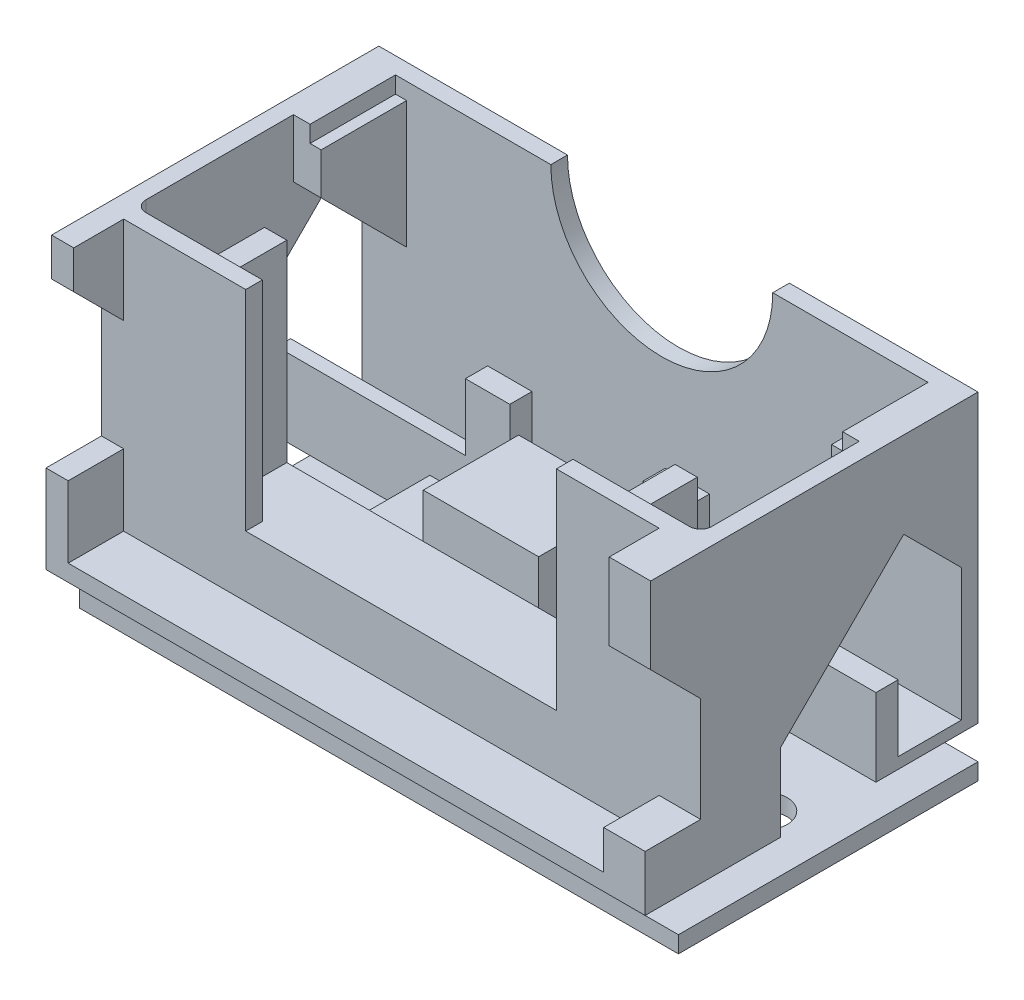
SolidWorks part; units mm, degrees
note: The reader was unsure of these and kept them because the rebuilt part matched: shared geometry of "Sketch4<4>", "Sketch5<3>", "Sketch4<3>", "Sketch17<3>", "Sketch5<4>", "Sketch21<3>".
ref_plane "Front Plane" through (0, 0, 0) normal (0, 0, 1) x (1, 0, 0)
ref_plane "Top Plane" through (0, 0, 0) normal (0, 1, 0) x (1, 0, 0)
ref_plane "Right Plane" through (0, 0, 0) normal (1, 0, 0) x (0, 0, -1)
sketch "Sketch1" plane through (0, 0, 0) normal (0, 1, 0) x (1, 0, 0)
  line L1 (0, 0) -> (54, 0)
  line L2 (0, 0) -> (0, 27)
  line L3 (0, 27) -> (54, 27)
  line L4 (54, 0) -> (54, 27)
  dimension "D1" = 54
  dimension "D2" = 27
extrude "Boss-Extrude1" add sketch "Sketch1" along normal blind 1.5
sketch "Sketch2" plane through (0, 1.5, 0) normal (0, 1, 0) x (1, 0, 0)
  line L0 (0, 27) -> (0, 0) construction
  circle A0 centre (5.8, 13.5) radius 2.1
  point P5 (0, 13.5)
  dimension "D3" = 4.2
  dimension "D1" = 5.8
extrude "Cut-Extrude1" cut sketch "Sketch2" against normal up to next and the other way through all
ref_plane "Plane1" through (27, 0, 0) normal (-1, 0, 0) x (0, 0, 1)
mirror "Mirror1" about plane through (27, 0, 0) normal (-1, 0, 0) of "Cut-Extrude1"
sketch "Sketch3" plane through (0, 1.5, 0) normal (0, 1, 0) x (1, 0, 0)
  line L0 (54, 27) -> (0, 27) construction
  line L1 (13.8, 27) -> (40.2, 27)
  line L2 (13.8, 27) -> (13.8, -3)
  line L3 (13.8, -3) -> (40.2, -3)
  line L4 (40.2, 27) -> (40.2, -3)
  line L7 (0, 0) -> (54, 0) construction
  circle A0 centre (5.8, 13.5) radius 2.1 construction
  point P8 (27, 0)
  point P9 (27, -3)
  dimension "D1" = 8
  dimension "D2" = 3
extrude "Boss-Extrude2" add sketch "Sketch3" along normal blind 3
chamfer "Chamfer3" distance 3 angle 45 1 edges at (27, 1.5, 3)
sketch "Sketch4" plane through (0, 4.5, 0) normal (0, 1, 0) x (1, 0, 0)
  line L0 (54, 0) -> (54, 27) construction
  line L1 (0, 27) -> (54, 27)
  line L2 (0, 27) -> (0, 2)
  line L3 (0, 2) -> (54, 2)
  line L4 (54, 27) -> (54, 2)
  line L5 (0, 27) -> (0, 0) construction
  line L6 (0, 17.8) -> (54, 17.8)
  line L7 (0, 17.8) -> (0, 9.2)
  line L8 (0, 9.2) -> (54, 9.2)
  line L9 (54, 17.8) -> (54, 9.2)
  line L10 (40.2, 27) -> (13.8, 27) construction
  line L11 (0, 27) -> (0, 0) construction
  line L13 (32.2, 17.8) -> (21.8, 17.8)
  line L14 (32.2, 17.8) -> (32.2, 9.2)
  line L15 (32.2, 9.2) -> (21.8, 9.2)
  line L16 (21.8, 17.8) -> (21.8, 9.2)
  line L17 (40.2, 0) -> (54, 0) construction
  point P0 (0, 13.5)
  point P17 (0, 13.5)
  point P23 (27, 17.8)
  point P24 (27, 17.8)
  line M9 (13.8, 27) -> (13.8, -3)
  line M11 (40.2, -3) -> (40.2, 27)
  dimension "D1" = 8.6
  dimension "D2" = 21.8
  dimension "D3" = 2
extrude "Boss-Extrude3" add sketch "Sketch4" along normal blind 7
extrude "Boss-Extrude15" add sketch "Sketch4<4>" along normal blind 4 from surface at 7 contours L6 L16 L8 L14 starting at face at (27, 11.5, -13.8333)
sketch "Sketch4<4>" plane through (0, 4.5, 0) normal (0, 1, 0) x (1, 0, 0) same geometry as "Sketch4"
sketch "Sketch5" plane through (0, 11.5, 0) normal (0, 1, 0) x (1, 0, 0)
  line L0 (54, 9.2) -> (54, 2) construction
  line L1 (54, 2) -> (0, 2)
  line L2 (54, 2) -> (54, 3.5)
  line L3 (54, 3.5) -> (0, 3.5)
  line L4 (0, 2) -> (0, 3.5)
  line L5 (0, 9.2) -> (0, 2) construction
  line L6 (32.2, 9.2) -> (54, 9.2) construction
  line L7 (27, 0.825) -> (27, -0.825) construction
  line L16 (9.5, 9.2) -> (7.5, 9.2)
  line L17 (44.5, 3.5) -> (46.5, 3.5)
  line L18 (44.5, 3.5) -> (44.5, 9.2)
  line L19 (44.5, 9.2) -> (46.5, 9.2)
  line L20 (46.5, 3.5) -> (46.5, 9.2)
  line L21 (7.5, 3.5) -> (7.5, 9.2)
  line L22 (9.5, 3.5) -> (7.5, 3.5)
  line L23 (9.5, 3.5) -> (9.5, 9.2)
  line L27 (52.225, 2) -> (46.225, 2)
  line L29 (1.775, 2) -> (7.775, 2)
  line L33 (0, 27) -> (0, 17.8) construction
  line L34 (54, 27) -> (0, 27)
  line L35 (54, 27) -> (54, 25.5)
  line L36 (54, 25.5) -> (0, 25.5)
  line L37 (0, 27) -> (0, 25.5)
  line M16 (21.8, 9.2) -> (0, 9.2)
  line M20 (54, 9.2) -> (32.2, 9.2)
  dimension "D1" = 22
  dimension "D2" = 1.5
  dimension "D3" = 19.5
  dimension "D4" = 2
  dimension "D7" = 1.5
extrude "Boss-Extrude5" add sketch "Sketch5" along normal offset from surface (18.86 mm away) 25.86 contours L3 L4 L1 L2 up to face at (27, 4.5, 0.5) offset beyond the face yes
extrude "Boss-Extrude6" add sketch "Sketch5<3>" along normal offset from surface (17.36 mm away) 1.5 contours L3 L20 L18 M20 | L3 L23 L21 M16 up to face at (27, 30.36, -2.75)
sketch "Sketch5<3>" plane through (0, 11.5, 0) normal (0, 1, 0) x (1, 0, 0) same geometry as "Sketch5"
extrude "Boss-Extrude12" add sketch "Sketch4<3>" along normal offset from surface (3.86 mm away) 20.5 contours L16 L6 L8 M9 | L6 L14 L8 M11 up to face at (45.5, 28.86, -6.35)
sketch "Sketch4<3>" plane through (0, 4.5, 0) normal (0, 1, 0) x (1, 0, 0) same geometry as "Sketch4"
sketch "Sketch17" plane through (0, 0, -2) normal (0, 0, 1) x (1, 0, 0)
  line L0 (54, 30.36) -> (54, 4.5) construction
  line L1 (0, 4.5) -> (54, 4.5)
  line L2 (0, 4.5) -> (0, 6)
  line L3 (0, 6) -> (54, 6)
  line L4 (54, 4.5) -> (54, 6)
  line L5 (54, 30.36) -> (0, 30.36) construction
  line L10 (0, 30.36) -> (2, 30.36)
  line L11 (0, 30.36) -> (0, 6)
  line L12 (0, 6) -> (2, 6)
  line L13 (2, 30.36) -> (2, 6)
  line L14 (2, 22.43) -> (0, 22.43)
  line L15 (2, 22.43) -> (2, 12.43)
  line L16 (2, 12.43) -> (0, 12.43)
  line L17 (0, 22.43) -> (0, 12.43)
  line L23 (54, 6) -> (50.26, 6)
  line L24 (54, 30.36) -> (50.26, 30.36)
  line L25 (54, 30.36) -> (54, 18.93)
  line L26 (54, 18.93) -> (50.26, 18.93)
  line L27 (50.26, 30.36) -> (50.26, 18.93)
  line L28 (54, 6) -> (54, 9.5)
  line L29 (54, 9.5) -> (50.26, 9.5)
  line L30 (50.26, 6) -> (50.26, 9.5)
  point P18 (2, 17.43)
  point P20 (52.13, 18.93)
  line M21 (0, 4.5) -> (13.8, 4.5)
  line M22 (13.8, 4.5) -> (40.2, 4.5)
  line M23 (40.2, 4.5) -> (54, 4.5)
  line M24 (54, 4.5) -> (54, 30.36)
  line M25 (54, 30.36) -> (0, 30.36)
  line M26 (0, 30.36) -> (0, 4.5)
  dimension "D1" = 1.5
  dimension "D2" = 48.26
  dimension "D3" = 2
  dimension "D4" = 10
  dimension "D5" = 11.43
  dimension "D6" = 11.43
  dimension "D7" = 5
extrude "Boss-Extrude13" add sketch "Sketch17" along normal up to vertex (4 mm away) contours L13 L16 L3 M26 | L3 M26 M21 M22 M23 M24 | L28 L23 L30 L29
extrude "Boss-Extrude16" add sketch "Sketch17<3>" along normal offset from surface (4.5 mm away) 0.5 contours L14 L13 M25 M26 | L27 L26 M25 M24 up to face at (26.652, 7.386, 3)
sketch "Sketch17<3>" plane through (0, 0, -2) normal (0, 0, 1) x (1, 0, 0) same geometry as "Sketch17"
chamfer "Chamfer7" distance 4.5 angle 45 2 edges at (52.13, 18.93, 2.5) (1, 22.43, 2.5)
extrude "Boss-Extrude8" add sketch "Sketch5<4>" along normal up to surface (18.86 mm away)
sketch "Sketch5<4>" plane through (0, 11.5, 0) normal (0, 1, 0) x (1, 0, 0) same geometry as "Sketch5"
sketch "Sketch10" plane through (0, 0, 0) normal (-1, 0, 0) x (0, 0, 1)
  line L0 (-3.5, 30.36) -> (-25.5, 30.36)
  line L1 (-3.5, 30.36) -> (-3.5, 11.5) construction
  line L2 (-25.5, 30.36) -> (-25.5, 11.5) construction
  line L3 (-25.5, 30.36) -> (-25.5, 11.5)
  line L6 (-3.5, 11.5) -> (-3.5, 30.36)
  line L8 (-9.2, 11.5) -> (-3.5, 11.5) construction
  line L9 (-3.5, 30.36) -> (-9.2, 30.36)
  line L10 (-3.5, 30.36) -> (-3.5, 11.5)
  line L11 (-3.5, 11.5) -> (-9.2, 11.5)
  line L12 (-9.2, 30.36) -> (-9.2, 11.5)
  line L13 (-9.2, 28.86) -> (-9.2, 11.5) construction
  line L14 (-25.5, 11.5) -> (-17.8, 11.5) construction
  line L15 (-25.5, 30.36) -> (-19.35, 30.36)
  line L16 (-25.5, 30.36) -> (-25.5, 11.5)
  line L17 (-25.5, 11.5) -> (-19.35, 11.5)
  line L19 (2.5, 30.36) -> (-3.5, 30.36) construction
  line L21 (-25.5, 27.8) -> (-9.2, 11.5)
  dimension "D1" = 0
  dimension "D4" = 45
extrude "Boss-Extrude9" add sketch "Sketch10" against normal blind 1.5
mirror "Mirror3" about plane through (27, 0, 0) normal (-1, 0, 0) of "Boss-Extrude9"
sketch "Sketch18" plane through (0, 30.36, 0) normal (0, 1, 0) x (1, 0, 0)
  line L0 (52.5, 25.5) -> (1.5, 25.5) construction
  line L1 (0, 25.5) -> (4, 25.5)
  line L2 (0, 25.5) -> (0, 17.8)
  line L3 (0, 17.8) -> (4, 17.8)
  line L4 (4, 25.5) -> (4, 17.8)
  line L5 (27, 0.825) -> (27, -0.825) construction
  line L8 (0, 17.8) -> (21.8, 17.8) construction
  line L9 (54, 17.8) -> (50, 17.8)
  line L10 (50, 25.5) -> (50, 17.8)
  line L11 (54, 25.5) -> (50, 25.5)
  line L12 (54, 25.5) -> (54, 17.8)
  line L13 (0, -2.5) -> (0, 27) construction
  dimension "D1" = 23
extrude "Boss-Extrude14" add sketch "Sketch18" against normal blind 13
chamfer "Chamfer6" distance 7.75 angle 45 2 edges at (2, 17.36, -17.8) (52, 17.36, -17.8)
sketch "Sketch20" plane through (0, 30.36, 0) normal (0, 1, 0) x (1, 0, 0)
  line L0 (0, 17.8) -> (21.8, 17.8) construction
  line L1 (4, 25.5) -> (3, 25.5)
  line L2 (4, 25.5) -> (4, 17.8)
  line L3 (4, 17.8) -> (3, 17.8)
  line L4 (3, 25.5) -> (3, 17.8)
  line L5 (27, 0.825) -> (27, -0.825) construction
  line L6 (50, 17.8) -> (51, 17.8)
  line L7 (51, 25.5) -> (51, 17.8)
  line L8 (50, 25.5) -> (51, 25.5)
  line L9 (50, 25.5) -> (50, 17.8)
  dimension "D1" = 1
extrude "Cut-Extrude7" cut sketch "Sketch20" against normal up to surface (1.5 mm away) up to face at (8.5, 28.86, -6.35)
sketch "Sketch12" plane through (0, 0, -2) normal (0, 0, 1) x (1, 0, 0)
  line L0 (50.26, 30.36) -> (2, 30.36) construction
  line L1 (13, 30.36) -> (41, 30.36)
  line L3 (13, 30.36) -> (13, 11.5)
  line L4 (13, 11.5) -> (41, 11.5)
  line L5 (41, 30.36) -> (41, 11.5)
  line L6 (52.5, 30.36) -> (1.5, 30.36) construction
  line L7 (44.5, 11.5) -> (9.5, 11.5) construction
  point P11 (27, 30.36)
  point P12 (27, 30.36)
  dimension "D1" = 28
extrude "Cut-Extrude2" cut sketch "Sketch12" against normal up to surface (7.2 mm away) up to face at (44.3, 12.8127, -9.2)
sketch "Sketch14" plane through (0, 0, -27) normal (0, 0, -1) x (-1, 0, 0)
  line L0 (-54, 30.36) -> (0, 30.36) construction
  circle A0 centre (-27, 30.36) radius 10
  dimension "D1" = 20
extrude "Cut-Extrude3" cut sketch "Sketch14" against normal blind 10
sketch "Sketch15" plane through (0, 11.5, 0) normal (0, 1, 0) x (1, 0, 0)
  line L0 (54, 25.5) -> (54, 17.8) construction
  line L1 (21, 17.8) -> (17, 17.8)
  line L2 (21, 17.8) -> (21, 19.8)
  line L3 (21, 19.8) -> (17, 19.8)
  line L4 (17, 17.8) -> (17, 19.8)
  line L6 (54, 25.5) -> (0, 25.5) construction
  line L7 (0, 17.8) -> (21.8, 17.8) construction
  dimension "D1" = 37
  dimension "D2" = 4
  dimension "D4" = 5.7
extrude "Boss-Extrude11" add sketch "Sketch15" along normal blind 6
mirror "Mirror5" about plane through (27, 0, 0) normal (-1, 0, 0) of "Boss-Extrude11"
sketch "Sketch21" plane through (0, 11.5, 0) normal (0, 1, 0) x (1, 0, 0)
  line L0 (54, 25.5) -> (54, 17.8) construction
  line L1 (0, 25.5) -> (54, 25.5)
  line L2 (0, 25.5) -> (0, 19.8)
  line L3 (0, 19.8) -> (54, 19.8)
  line L4 (54, 25.5) -> (54, 19.8)
  line L5 (33, 19.8) -> (37, 19.8) construction
  line L6 (17, 19.8) -> (17, 17.8) construction
  line L7 (0, 25.5) -> (17, 25.5)
  line L8 (0, 25.5) -> (0, 19.05)
  line L9 (0, 19.05) -> (17, 19.05)
  line L10 (17, 25.5) -> (17, 19.05)
  line M6 (33, 19.8) -> (37, 19.8)
  line M9 (54, 17.8) -> (54, 25.5)
  line M10 (54, 25.5) -> (0, 25.5)
  line M11 (0, 25.5) -> (0, 17.8)
  line M13 (17, 17.8) -> (17, 19.8)
  line M14 (17, 19.8) -> (21, 19.8)
  dimension "D1" = 0.75
extrude "Cut-Extrude8" cut sketch "Sketch21" against normal blind 6 contours L10 L3 M10 M14 M6 M9 | L10 L1 L3 M11 | L9 L3 M11 M13
extrude "Cut-Extrude9" cut sketch "Sketch21<3>" against normal up to surface (1 mm away) from surface at -6 contours L10 L1 L3 M11 | L9 L3 M11 M13 up to face at (6.9, 4.5, -3.1) starting at face at (23.6667, 5.5, -21.45)
sketch "Sketch21<3>" plane through (0, 11.5, 0) normal (0, 1, 0) x (1, 0, 0) same geometry as "Sketch21"
fillet "Fillet7" radius 1 2 edges at (1.5, 20.93, -3.5) (52.5, 20.93, -3.5)
